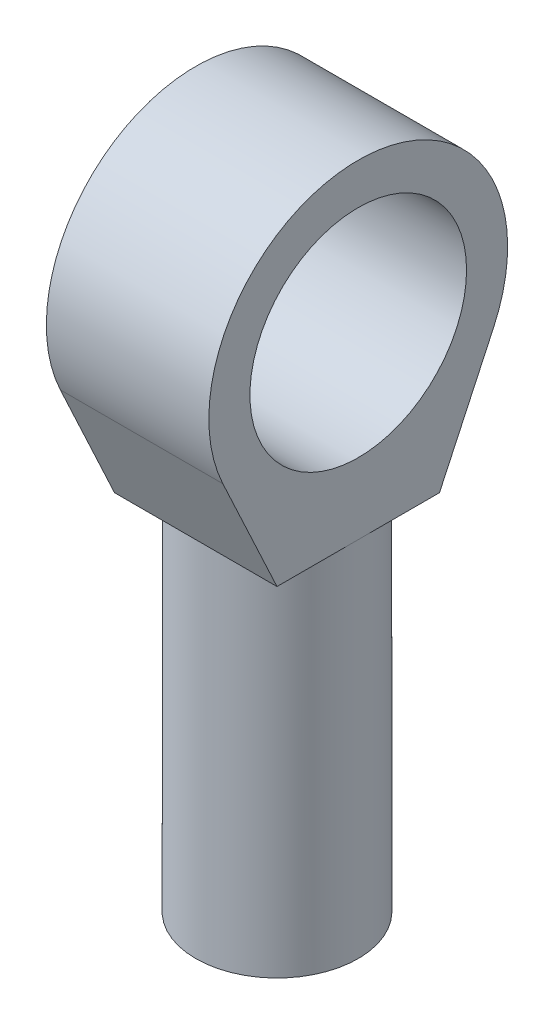
SolidWorks part; units mm, degrees
ref_plane "Front Plane" through (0, 0, 0) normal (0, 0, 1) x (1, 0, 0)
ref_plane "Top Plane" through (0, 0, 0) normal (0, 1, 0) x (1, 0, 0)
ref_plane "Right Plane" through (0, 0, 0) normal (1, 0, 0) x (0, 0, -1)
sketch "Sketch2" plane through (0, 0, 0) normal (0, 1, 0) x (1, 0, 0)
  circle A0 centre (0, 0) radius 9.525
  dimension "D1" = 19.05
extrude "Boss-Extrude1" add sketch "Sketch2" along normal blind 42.545
sketch "Sketch3" plane through (0, 0, 0) normal (1, 0, 0) x (0, 0, -1)
  line L0 (-9.525, 42.545) -> (-15.875, 56.1626)
  line L1 (9.525, 42.545) -> (15.875, 56.1626)
  line L2 (-9.525, 42.545) -> (-9.525, 0) construction
  line L5 (-9.525, 42.545) -> (9.525, 42.545)
  arc A0 (-15.875, 56.1626) -> (15.875, 56.1626) centre (0, 63.5653) cw
  circle A1 centre (0, 63.5653) radius 12.7
  dimension "D3" = 25.4
  dimension "D1" = 155
  dimension "D2" = 31.75
extrude "Boss-Extrude2" add sketch "Sketch3" along normal blind 9.525 and the other way blind 9.525
